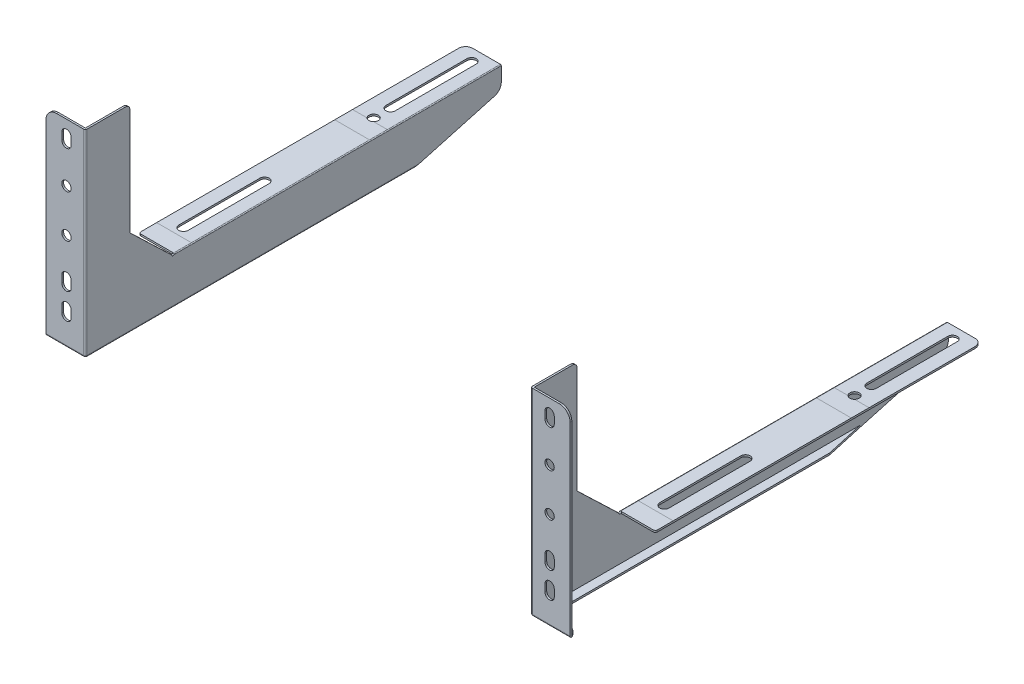
SolidWorks part; units mm, degrees
ref_plane "Front Plane" through (0, 0, 0) normal (0, 0, 1) x (1, 0, 0)
ref_plane "Top Plane" through (0, 0, 0) normal (0, 1, 0) x (1, 0, 0)
ref_plane "Right Plane" through (0, 0, 0) normal (1, 0, 0) x (0, 0, -1)
sketch "Sketch1" plane through (0, 0, 0) normal (1, 0, 0) x (0, 0, -1)
  line L0 (0, 0) -> (368, 0) construction
  line L1 (0, 0) -> (368, 0)
  line L2 (0, 0) -> (0, 52)
  line L3 (100, 52) -> (467, 52)
  line L5 (467, 52) -> (467.0003, 35)
  line L7 (368, 0) -> (459.6668, 25.3611)
  line L10 (0, 0) -> (50, 0)
  line L11 (0, 0) -> (0, 222)
  line L12 (0, 222) -> (45, 222)
  line L13 (50, 97) -> (50, 217)
  line L15 (50, 97) -> (97, 52)
  arc A0 (459.6668, 25.3611) -> (467.0003, 35) centre (457.0003, 34.9991) ccw
  arc A1 (50, 217) -> (45, 222) centre (45, 217) ccw
  arc A2 (97, 52) -> (100, 52) centre (98.5, 52) ccw
  dimension "D5" = 10
  dimension "D14" = 10
  dimension "D15" = 1.5
  dimension "D1" = 467
  dimension "D2" = 368
  dimension "D3" = 52
  dimension "D4" = 17
  dimension "D6" = 95.1104
  dimension "D7" = 459.6668
  dimension "D8" = 50
  dimension "D9" = 222
  dimension "D10" = 45
  dimension "D11" = 97
  dimension "D12" = 97
  dimension "D13" = 52
  dimension "D16" = 47
extrude "Boss-Extrude1" add sketch "Sketch1" along normal blind 2 contours A2 L15 L13 A1 L12 L11 L2 L1 L7 A0 L5 L3 region at (0, 26, -5.1708)
sketch "Sketch2" plane through (0, 0, 0) normal (0, 0, 1) x (1, 0, 0)
  line L0 (16, 207) -> (16, 199)
  line L1 (0, 0) -> (44.2119, 0)
  line L2 (0, 0) -> (0, 222)
  line L3 (0, 222) -> (32.2119, 222)
  line L4 (44.2119, 0) -> (44.2119, 210)
  line L5 (26.5, 207) -> (26.5, 199)
  line L6 (21.25, 222) -> (21.25, 103.75) construction
  line L11 (26.5, 68) -> (26.5, 60)
  line L12 (26.5, 39) -> (26.5, 31)
  line L13 (21.25, 103.75) -> (21.25, 0) construction
  line L14 (16, 68) -> (16, 60)
  line L15 (16, 39) -> (16, 31)
  arc A0 (44.2119, 210) -> (32.2119, 222) centre (32.2119, 210) ccw
  arc A1 (26.5, 207) -> (16, 207) centre (21.25, 207) ccw
  arc A2 (16, 199) -> (26.5, 199) centre (21.25, 199) ccw
  circle A3 centre (21.25, 157) radius 5.25
  circle A4 centre (21.25, 109) radius 5.25
  arc A11 (16, 31) -> (26.5, 31) centre (21.25, 31) ccw
  arc A12 (26.5, 39) -> (16, 39) centre (21.25, 39) ccw
  arc A13 (26.5, 68) -> (16, 68) centre (21.25, 68) ccw
  arc A14 (16, 60) -> (26.5, 60) centre (21.25, 60) ccw
  dimension "D2" = 24
  dimension "D1" = 10.5
  dimension "D3" = 15
  dimension "D4" = 10.5
  dimension "D8" = 222
  dimension "D11" = 10.5
  dimension "D13" = 10.5
  dimension "D15" = 5.25
  dimension "D16" = 5.25
  dimension "D23" = 68
  dimension "D24" = 90
  dimension "D25" = 5.25
  dimension "D21" = 5.25
  dimension "D22" = 60
  dimension "D5" = 8
  dimension "D6" = 16
  dimension "D7" = 44.2119
  dimension "D9" = 8
  dimension "D10" = 90
  dimension "D12" = 42
  dimension "D14" = 48
  dimension "D17" = 29
  dimension "D18" = 8
  dimension "D19" = 29
  dimension "D20" = 8
  dimension "D26" = 39
extrude "Boss-Extrude2" add sketch "Sketch2" against normal blind 2
sketch "Sketch3" plane through (0, 0, 0) normal (0, -1, 0) x (1, 0, 0)
  line L0 (0, -10) -> (0, -368)
  line L1 (0, 0) -> (44.2119, 0)
  line L2 (0, 0) -> (0, -10)
  line L3 (11.8025, -10) -> (32.2119, -10)
  line L4 (44.2119, 0) -> (44.2119, -2)
  line L5 (0, 0) -> (11.8025, 0)
  line L6 (0, 0) -> (0, -368)
  line L7 (0, -368) -> (2, -368)
  line L8 (11.8025, -10) -> (11.8025, -324)
  line L9 (11.8025, -324) -> (2, -368)
  arc A0 (31.9511, -10) -> (32.2119, -10) centre (32.0815, 3.1956) ccw
  arc A1 (31.9511, -10) -> (44.2119, -2) centre (32.0898, 3.183) ccw
  line M10 (0, 0) -> (0, -368)
  line M11 (0, -368) -> (2, -368)
  line M12 (2, -368) -> (2, -2)
  line M13 (2, -2) -> (44.2119, -2)
  line M14 (44.2119, -2) -> (44.2119, 0)
  line M15 (44.2119, 0) -> (0, 0)
  dimension "D2" = 13.1962
  dimension "D5" = 20.2791
  dimension "D6" = 13.1837
  dimension "D1" = 10
  dimension "D3" = 2
  dimension "D4" = 44.2119
  dimension "D7" = 14.6399
  dimension "D8" = 44
extrude "Boss-Extrude3" add sketch "Sketch3" against normal blind 2 contours A0 A1 L9 L8 L3 M13 M12 | L1 M15 M10 M11 M12 M13 M14 region at (0.3706, 0, -5) region at (8.0634, 0, -163.3791)
sketch "Sketch4" plane through (0, 52, 0) normal (0, 1, 0) x (1, 0, 0)
  line L0 (20, 102.5) -> (20, 464.9391) construction
  line L1 (0, 100) -> (37.5, 100)
  line L2 (0, 100) -> (0, 467)
  line L3 (0, 467) -> (32, 467)
  line L4 (40, 102.5) -> (40, 459)
  line L5 (14.75, 453.699) -> (14.75, 362.699)
  line L6 (25.25, 453.699) -> (25.25, 362.699)
  line L7 (14.75, 221.199) -> (14.75, 130.199)
  line L8 (25.25, 221.199) -> (25.25, 130.199)
  arc A0 (37.5, 100) -> (40, 102.5) centre (37.5, 102.5) ccw
  arc A1 (40, 459) -> (32, 467) centre (32, 459) ccw
  arc A2 (25.25, 453.699) -> (14.75, 453.699) centre (20, 453.699) ccw
  arc A3 (14.75, 362.699) -> (25.25, 362.699) centre (20, 362.699) ccw
  circle A4 centre (20, 343.699) radius 5.25
  arc A5 (25.25, 221.199) -> (14.75, 221.199) centre (20, 221.199) ccw
  arc A6 (14.75, 130.199) -> (25.25, 130.199) centre (20, 130.199) ccw
  dimension "D2" = 5
  dimension "D3" = 16
  dimension "D4" = 10.5
  dimension "D5" = 10.5
  dimension "D7" = 10.5
  dimension "D9" = 10.5
  dimension "D10" = 10.5
  dimension "D14" = 8
  dimension "D1" = 19
  dimension "D6" = 91
  dimension "D8" = 122.5
  dimension "D11" = 91
  dimension "D12" = 10.5
  dimension "D13" = 40
  dimension "D15" = 367
extrude "Boss-Extrude4" add sketch "Sketch4" against normal blind 2
fillet "Fillet1" radius 2 3 edges at (0, 111, 0) (22.106, 0, 0) (0, 0, -184)
fillet "Fillet2" radius 1 1 edges at (0, 52, -283.5)
ref_plane "Plane1" through (-250, 0, 0) normal (-1, 0, 0) x (0, 0, 1)
mirror "Mirror2" about plane through (-250, 0, 0) normal (-1, 0, 0) of bodies 104
sketch "Sketch5" plane through (0, 52, 0) normal (0, 1, 0) x (1, 0, 0)
  line L0 (-540, 120) -> (40, 120)
  line L1 (-540, 102.5) -> (-540, 459) construction
  line L2 (40, 102.5) -> (40, 459) construction
  line L3 (-502, 100) -> (-537.5, 100) construction
  line L4 (-540, 340) -> (40, 340)
  line L5 (-540, 320) -> (40, 320)
  line L6 (-532.2119, 0) -> (-502, 0) construction
  dimension "D1" = 20
  dimension "D2" = 20
  dimension "D3" = 340
split line "Split Line1"
